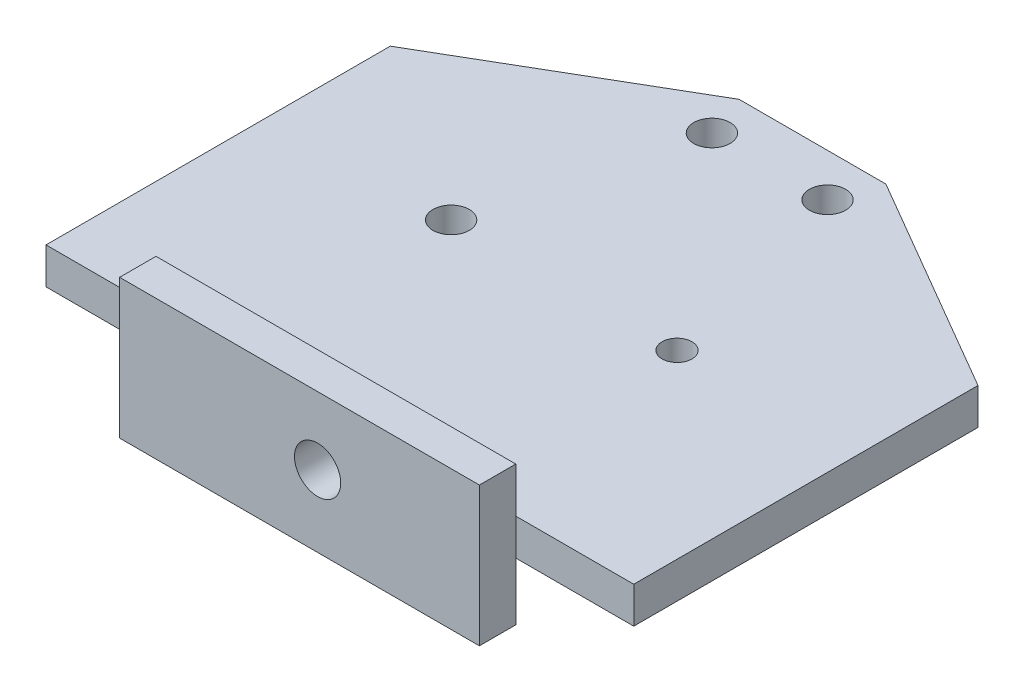
SolidWorks part; units mm, degrees
ref_plane "Alzado" through (0, 0, 0) normal (0, 0, 1) x (1, 0, 0)
ref_plane "Planta" through (0, 0, 0) normal (0, 1, 0) x (1, 0, 0)
ref_plane "Vista lateral" through (0, 0, 0) normal (1, 0, 0) x (0, 0, -1)
sketch "Croquis1" plane through (0, 0, 0) normal (0, 1, 0) x (1, 0, 0)
  line L0 (-6.0558, 19.5) -> (-24.25, 8.9065)
  line L1 (-6.0558, 19.5) -> (6.0558, 19.5)
  line L2 (-24.25, 8.9065) -> (-24.25, -19.5)
  line L3 (-24.25, -19.5) -> (24.25, -19.5)
  line L4 (24.25, 8.9065) -> (24.25, -19.5)
  line L5 (-24.25, 19.5) -> (24.25, -19.5) construction
  line L6 (-24.25, -19.5) -> (24.25, 19.5) construction
  line L7 (6.0558, 19.5) -> (24.25, 8.9065)
  line L8 (0, 19.5) -> (0, -19.5) construction
  line L9 (-24.25, 19.5) -> (-24.25, 8.9065) construction
  line L10 (-6.0558, 19.5) -> (-24.25, 19.5) construction
  line L11 (6.0558, 19.5) -> (24.25, 19.5) construction
  line L12 (24.25, 19.5) -> (24.25, 8.9065) construction
  line L13 (-24.25, 8.9065) -> (24.25, 8.9065) construction
  line L14 (4.77, 15.97) -> (-4.77, 15.97) construction
  line L15 (-9.32, -1) -> (24.25, -1) construction
  circle A0 centre (-4.77, 15.97) radius 1.5
  circle A1 centre (4.77, 15.97) radius 1.5
  circle A2 centre (-9.32, -1) radius 1.5
  circle A3 centre (9.32, -1) radius 1.2316
  point P0 (0, 0)
  point P16 (0, 15.97)
  dimension "D5" = 3
  dimension "D4" = 3
  dimension "D1" = 48.5
  dimension "D2" = 39
  dimension "D3" = 149.79
  dimension "D6" = 9.54
  dimension "D7" = 3.53
  dimension "D8" = 33.57
  dimension "D9" = 16.97
extrude "Saliente-Extruir1" add sketch "Croquis1" along normal blind 3
sketch "Croquis2" plane through (0, 0, 19.5) normal (0, 0, 1) x (1, 0, 0)
  line L1 (-15.1739, 6.7212) -> (14.5131, 6.7212)
  line L2 (-15.1739, 6.7212) -> (-15.1739, -4.7731)
  line L3 (-15.1739, -4.7731) -> (14.5131, -4.7731)
  line L4 (14.5131, 6.7212) -> (14.5131, -4.7731)
extrude "Saliente-Extruir2" add sketch "Croquis2" along normal blind 3
sketch "Croquis3" plane through (0, 0, 22.5) normal (0, 0, 1) x (1, 0, 0)
  circle A0 centre (1.1625, 1.1345) radius 1.909
extrude "Cortar-Extruir1" cut sketch "Croquis3" against normal blind 3
